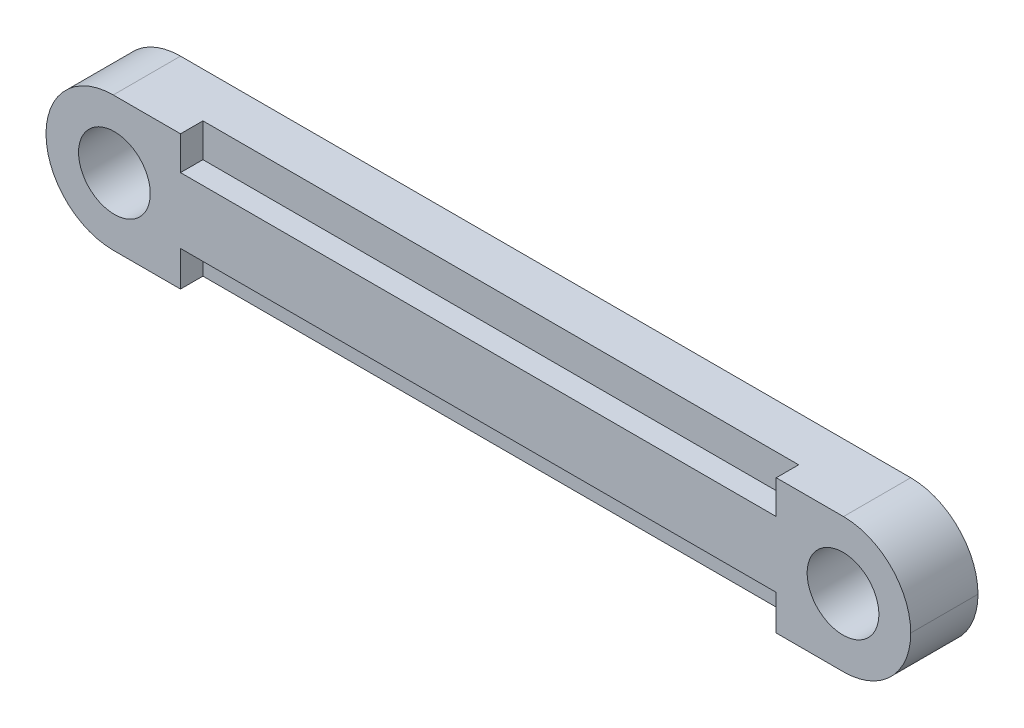
SolidWorks part; units mm, degrees
ref_plane "Płaszczyzna przednia" through (0, 0, 0) normal (0, 0, 1) x (1, 0, 0)
ref_plane "Płaszczyzna górna" through (0, 0, 0) normal (0, 1, 0) x (1, 0, 0)
ref_plane "Płaszczyzna prawa" through (0, 0, 0) normal (1, 0, 0) x (0, 0, -1)
sketch "Szkic1" plane through (0, 0, 0) normal (0, 0, 1) x (1, 0, 0)
  line L0 (4.274, 13.9333) -> (4.274, 7.9333)
  line L1 (-34.2996, 13.9333) -> (4.274, 13.9333)
  line L2 (-34.2996, 13.9333) -> (-34.2996, 7.9333)
  line L3 (-34.2996, 7.9333) -> (4.274, 7.9333)
  dimension "D1" = 6
extrude "Dodanie-wyciągnięcie1" add sketch "Szkic1" along normal blind 2
sketch "Szkic3" plane through (0, 0, 2) normal (0, 0, 1) x (1, 0, 0)
  circle A0 centre (-31.2487, 10.9432) radius 1.6
  circle A1 centre (1.2513, 10.9432) radius 1.6
  dimension "D1" = 3.2
  dimension "D2" = 3.2
extrude "Wytnij-wyciągnięcie2" cut sketch "Szkic3" against normal through all and the other way blind 1
sketch "Szkic4" plane through (0, 0, 2) normal (0, 0, 1) x (1, 0, 0)
  line L0 (4.274, 7.9333) -> (4.274, 13.9333) construction
  line L1 (-34.2996, 13.9333) -> (-28.2996, 13.9333)
  line L2 (-34.2996, 13.9333) -> (-34.2996, 7.9333)
  line L3 (-34.2996, 7.9333) -> (-28.2996, 7.9333)
  line L4 (-28.2996, 13.9333) -> (-28.2996, 12.4333)
  line L5 (4.274, 13.9333) -> (-1.726, 13.9333)
  line L6 (4.274, 13.9333) -> (4.274, 7.9333)
  line L7 (4.274, 7.9333) -> (-1.726, 7.9333)
  line L8 (-1.726, 13.9333) -> (-1.726, 12.4333)
  line L9 (-28.2996, 10.9333) -> (-1.726, 10.9333) construction
  line L10 (-28.2996, 12.4333) -> (-1.726, 12.4333)
  line L11 (-28.2996, 9.5047) -> (-1.726, 9.5047)
  line L12 (-28.2996, 9.5047) -> (-28.2996, 7.9333)
  line L13 (-1.726, 9.5047) -> (-1.726, 7.9333)
  dimension "D1" = 6
  dimension "D2" = 6
  dimension "D3" = 0
extrude "Dodanie-wyciągnięcie2" add sketch "Szkic4" along normal blind 1
sketch "Szkic5" plane through (0, 0, 0) normal (0, 0, -1) x (-1, 0, 0)
  circle A1 centre (-1.2513, 10.9432) radius 1.6
  circle A2 centre (31.2487, 10.9432) radius 1.6
extrude "Wytnij-wyciągnięcie3" cut sketch "Szkic5" against normal through all
fillet "Zaokrąglenie1" radius 3 4 edges at (-34.2996, 7.9333, 1.5) (-34.2996, 13.9333, 1.5) (4.274, 7.9333, 1.5) (4.274, 13.9333, 1.5)
